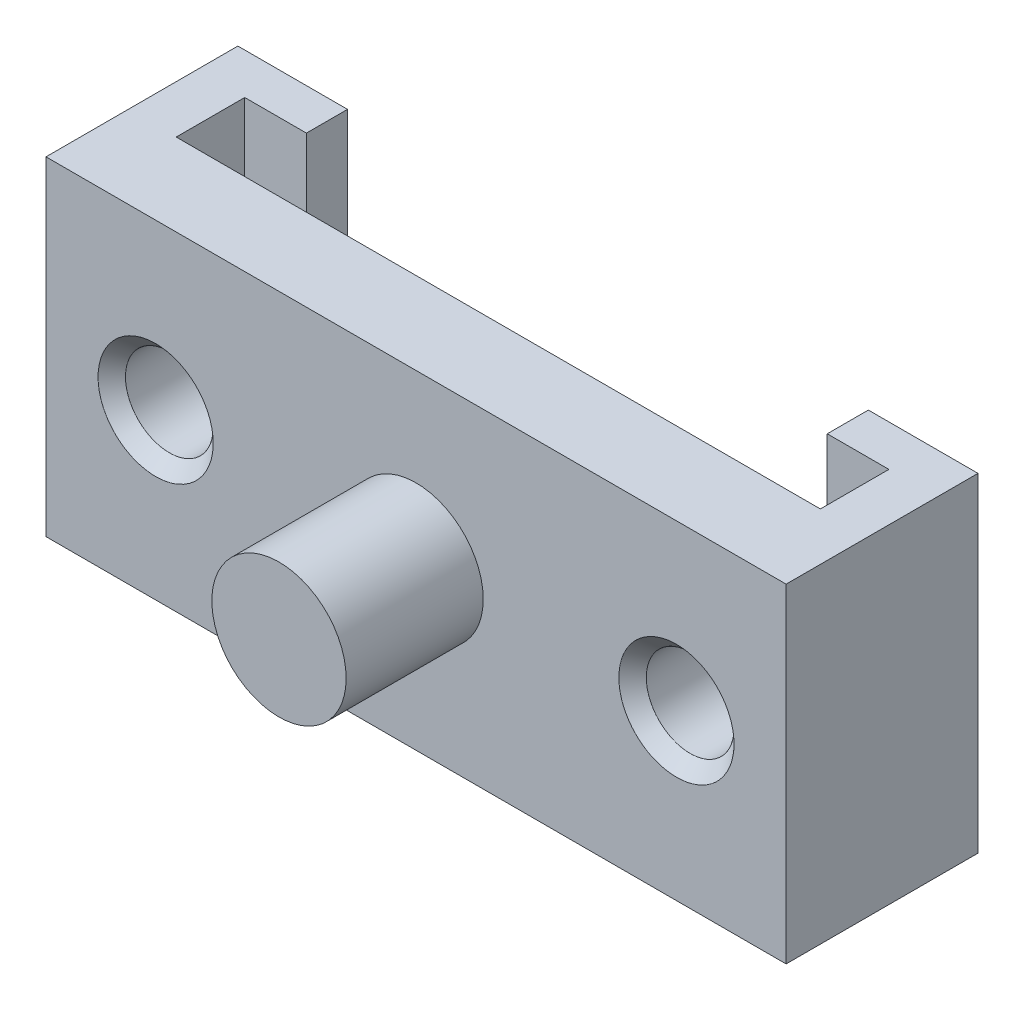
SolidWorks part; units mm, degrees
ref_plane "Front Plane" through (0, 0, 0) normal (0, 0, 1) x (1, 0, 0)
ref_plane "Top Plane" through (0, 0, 0) normal (0, 1, 0) x (1, 0, 0)
ref_plane "Right Plane" through (0, 0, 0) normal (1, 0, 0) x (0, 0, -1)
sketch "Sketch1" plane through (0, 0, 0) normal (0, 0, 1) x (1, 0, 0)
  line L0 (13.5, 0) -> (13.5, -12) construction
  line L1 (0, 0) -> (27, 0)
  line L2 (0, 0) -> (0, -12)
  line L3 (0, -12) -> (27, -12)
  line L4 (27, 0) -> (27, -12)
extrude "Boss-Extrude1" add sketch "Sketch1" along normal blind 3
sketch "Sketch2" plane through (0, 0, 3) normal (0, 0, 1) x (1, 0, 0)
  line L0 (13.5, 0) -> (13.5, -12) construction
  line L1 (27, 0) -> (0, 0) construction
  line L2 (0, -12) -> (27, -12) construction
  circle A0 centre (13.5, -6) radius 2.45
extrude "Boss-Extrude2" add sketch "Sketch2" along normal blind 5
sketch "Sketch3" plane through (0, 0, 0) normal (0, 0, -1) x (-1, 0, 0)
  line L0 (-27, 0) -> (0, 0) construction
  line L1 (0, -12) -> (-1.75, -12)
  line L2 (0, -12) -> (0, 0)
  line L3 (0, 0) -> (-1.75, 0)
  line L4 (-1.75, -12) -> (-1.75, 0)
  line L6 (-27, -12) -> (-25.25, -12)
  line L7 (-27, -12) -> (-27, 0)
  line L8 (-27, 0) -> (-25.25, 0)
  line L9 (-25.25, -12) -> (-25.25, 0)
extrude "Boss-Extrude3" add sketch "Sketch3" along normal blind 2.5
sketch "Sketch4" plane through (0, 0, 0) normal (0, 0, -1) x (-1, 0, 0)
  line L0 (-1.75, -6) -> (-4, -6) construction
  line L1 (-1.75, 0) -> (-1.75, -12) construction
  line L2 (-25.25, -6) -> (-23, -6) construction
  line L3 (-25.25, -12) -> (-25.25, 0) construction
  circle A0 centre (-4, -6) radius 1.6
  circle A1 centre (-23, -6) radius 1.6
extrude "Cut-Extrude1" cut sketch "Sketch4" against normal through all
sketch "Sketch5" plane through (0, 0, -2.5) normal (0, 0, -1) x (-1, 0, 0)
  line L1 (0, 0) -> (-4, 0)
  line L2 (0, 0) -> (0, -12)
  line L3 (0, -12) -> (-4, -12)
  line L4 (-4, 0) -> (-4, -12)
  line L5 (-27, 0) -> (-23, 0)
  line L6 (-27, 0) -> (-27, -12)
  line L7 (-27, -12) -> (-23, -12)
  line L8 (-23, 0) -> (-23, -12)
extrude "Boss-Extrude4" add sketch "Sketch5" along normal blind 1.5
fillet "Fillet1" radius 0.5 2 edges at (24.6, -6, 3) (5.6, -6, 3)
